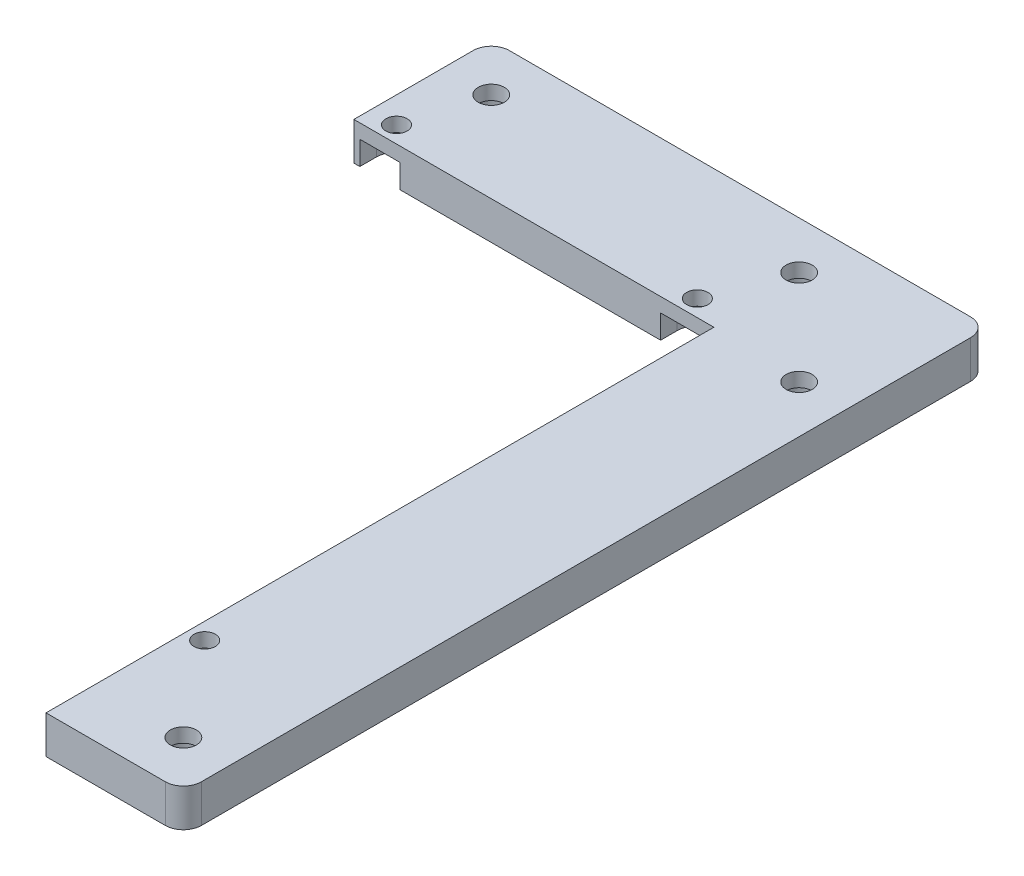
SolidWorks part; units mm, degrees
ref_plane "Front Plane" through (0, 0, 0) normal (0, 0, 1) x (1, 0, 0)
ref_plane "Top Plane" through (0, 0, 0) normal (0, 1, 0) x (1, 0, 0)
ref_plane "Right Plane" through (0, 0, 0) normal (1, 0, 0) x (0, 0, -1)
sketch "Sketch1" plane through (0, 0, 0) normal (0, 1, 0) x (1, 0, 0)
  line L0 (-52.5, 56) -> (23.5, 56)
  line L1 (-52.5, -85) -> (48.6882, -85)
  line L2 (-52.5, -85) -> (-52.5, 81.1882)
  line L3 (-48.6882, 85) -> (48.6882, 85)
  line L4 (52.5, -81.1882) -> (52.5, 81.1882)
  line L5 (-52.5, -85) -> (52.5, 85) construction
  line L6 (-52.5, 85) -> (52.5, -85) construction
  line L7 (23.5, 56) -> (23.5, -85)
  arc A0 (48.6882, -85) -> (52.5, -81.1882) centre (48.6882, -81.1882) ccw
  arc A1 (48.6882, 85) -> (52.5, 81.1882) centre (48.6882, 81.1882) cw
  arc A2 (-52.5, 81.1882) -> (-48.6882, 85) centre (-48.6882, 81.1882) cw
  circle A3 centre (-42.5, 75) radius 2.75
  circle A4 centre (22.5, 75) radius 2.75
  circle A5 centre (42.5, -75) radius 2.75
  circle A6 centre (42.5, 55) radius 2.75
  circle A7 centre (-47, 59.5) radius 2.25
  circle A8 centre (16.5, 59.5) radius 2.25
  circle A9 centre (27, -55) radius 2.25
  point P0 (0, 0)
  point P32 (29.326, -59.6708)
  point P33 (18.4815, 61.1401)
  point P34 (-44.4923, 61.1401)
  dimension "D3" = 3.8118
  dimension "D6" = 10
  dimension "D14" = 5.5
  dimension "D1" = 105
  dimension "D2" = 170
  dimension "D4" = 141
  dimension "D5" = 76
  dimension "D7" = 10
  dimension "D8" = 10
  dimension "D9" = 10
  dimension "D10" = 10
  dimension "D11" = 10
  dimension "D12" = 30
  dimension "D13" = 30
  dimension "D15" = 3.5
  dimension "D16" = 3.5
  dimension "D17" = 3.5
  dimension "D18" = 30
  dimension "D19" = 7
extrude "Boss-Extrude1" add sketch "Sketch1" along normal blind 4 and the other way blind 4 contours A2 L2 L0 L7 L1 A0 L4 A1 L3 A9 A8 A7 A6 A5 A4 A3 region at (-50.5019, 0, -68.5941)
sketch "Sketch2" plane through (0, -4, 0) normal (0, -1, 0) x (1, 0, 0)
  line L0 (27, 59.25) -> (23.5, 59.25)
  line L1 (23.5, -56) -> (23.5, 85) construction
  line L2 (23.5, 59.25) -> (23.5, 50.75)
  line L3 (23.5, 50.75) -> (27, 50.75)
  line L4 (12.25, -59.5) -> (12.25, -56)
  line L5 (-52.5, -56) -> (23.5, -56) construction
  line L6 (12.25, -56) -> (20.75, -56)
  line L7 (20.75, -56) -> (20.75, -59.5)
  line L8 (-51.25, -59.5) -> (-51.25, -56)
  line L9 (-51.25, -56) -> (-42.75, -56)
  line L10 (-42.75, -56) -> (-42.75, -59.5)
  circle A0 centre (42.5, 75) radius 4.25
  arc A1 (27, 50.75) -> (27, 59.25) centre (27, 55) ccw
  circle A2 centre (42.5, -55) radius 4.25
  circle A3 centre (22.5, -75) radius 4.25
  arc A4 (12.25, -59.5) -> (20.75, -59.5) centre (16.5, -59.5) ccw
  circle A5 centre (-42.5, -75) radius 4.25
  arc A6 (-51.25, -59.5) -> (-42.75, -59.5) centre (-47, -59.5) ccw
  circle A7 centre (27, 55) radius 2.25 construction
  circle A8 centre (42.5, -55) radius 2.75 construction
  circle A9 centre (22.5, -75) radius 2.75 construction
  circle A10 centre (16.5, -59.5) radius 2.25 construction
  circle A11 centre (-42.5, -75) radius 2.75 construction
  circle A12 centre (-47, -59.5) radius 2.25 construction
extrude "Cut-Extrude1" cut sketch "Sketch2" against normal blind 5
